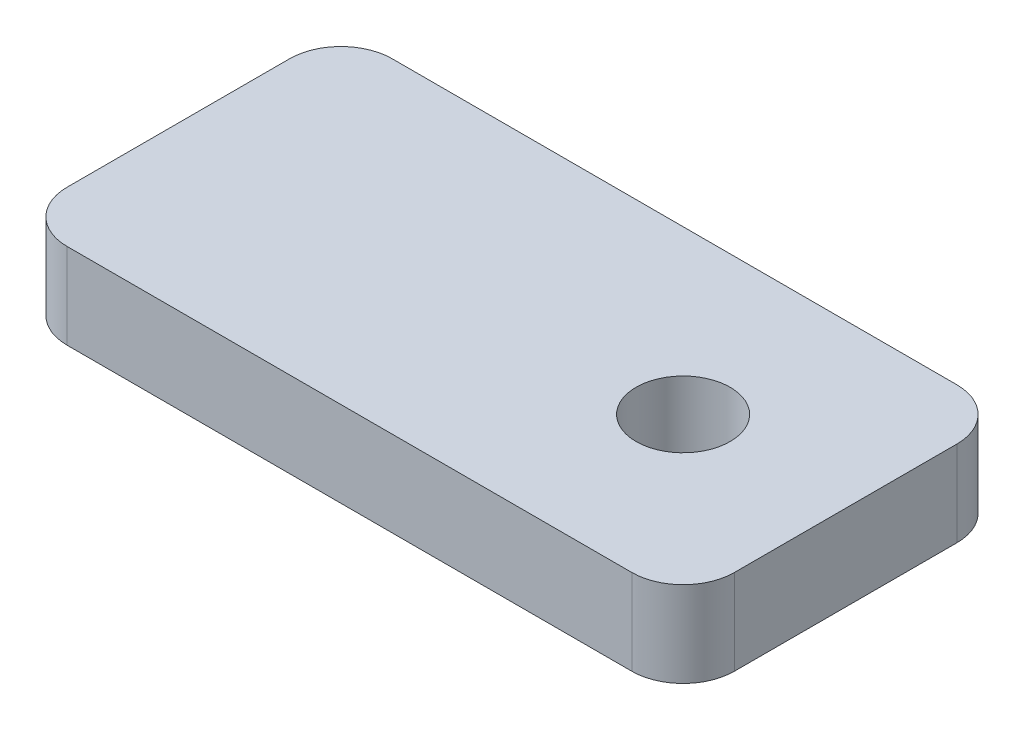
SolidWorks part; units mm, degrees
ref_plane "Top" through (0, 0, 0) normal (0, 0, 1) x (1, 0, 0)
ref_plane "Front" through (0, 0, 0) normal (0, 1, 0) x (1, 0, 0)
ref_plane "Right" through (0, 0, 0) normal (1, 0, 0) x (0, 0, -1)
sketch "Profile Sketch" plane through (0, 0, 0) normal (0, 1, 0) x (1, 0, 0)
  line L0 (0, -10) -> (0, 10) construction
  line L1 (-16.5, -9.5) -> (16.5, -9.5)
  line L2 (-19.5, -6.5) -> (-19.5, 6.5)
  line L3 (-16.5, 9.5) -> (16.5, 9.5)
  line L4 (19.5, -6.5) -> (19.5, 6.5)
  line L5 (-20, -10) -> (20, -10) construction
  line L6 (-20, -10) -> (-20, 10) construction
  line L7 (-20, 10) -> (20, 10) construction
  line L8 (20, -10) -> (20, 10) construction
  arc A0 (-16.5, -9.5) -> (-19.5, -6.5) centre (-16.5, -6.5) cw
  arc A1 (-16.5, 9.5) -> (-19.5, 6.5) centre (-16.5, 6.5) ccw
  arc A2 (19.5, 6.5) -> (16.5, 9.5) centre (16.5, 6.5) ccw
  arc A3 (16.5, -9.5) -> (19.5, -6.5) centre (16.5, -6.5) ccw
  point P24 (0, 0)
  dimension "Corner Radius" = 3
  dimension "D3" = 0.5
  dimension "D4" = 0.5
  dimension "D5" = 0.5
  dimension "D6" = 20
  dimension "D11" = 20
  dimension "D12" = 20
  dimension "D2" = 19.5
extrude "Profile" add sketch "Profile Sketch" against normal blind 5
sketch "Extension Sketch" plane through (0, 0, 0) normal (0, 1, 0) x (1, 0, 0)
  line L0 (-14.5, 9.5) -> (-16.5, 9.5)
  line L1 (-19.5, 6.5) -> (-19.5, -6.5)
  line L2 (-16.5, -9.5) -> (-14.5, -9.5)
  line L3 (-14.5, -9.5) -> (-14.5, 9.5)
  line L4 (-19.5, -6.5) -> (-19.5, 6.5) construction
  line L5 (-16.5, 9.5) -> (16.5, 9.5) construction
  line L6 (-16.5, -9.5) -> (16.5, -9.5) construction
  arc A0 (-19.5, -6.5) -> (-16.5, -9.5) centre (-16.5, -6.5) ccw
  arc A1 (-19.5, 6.5) -> (-16.5, 9.5) centre (-16.5, 6.5) cw
  dimension "D1" = 3
  dimension "D2" = 5
extrude "Extension Extrude" [suppressed] add sketch "Extension Sketch" along normal blind 5
hole_wizard "M5 Hole" positions "M5 Position Sketch" profile "M5 Profile Sketch" hole size "M5" standard "ANSI Metric" end condition through all
sketch "M5 Position Sketch" plane through (0, 0, 0) normal (0, 1, 0) x (1, 0, 0)
  line L0 (20, 10) -> (0, -10) construction
  point P0 (10, 0)
sketch "M5 Profile Sketch" plane through (10, 0, 0) normal (1, 0, 0) x (0, 0, 1)
  line L0 (0, 0) -> (0, 5)
  line L1 (0, 5) -> (2.75, 5)
  line L2 (2.75, 5) -> (2.75, 0)
  line L5 (2.75, 0) -> (0, 0)
  line L11 (0, -6.35) -> (0, 107.95) construction
  dimension "Thru Hole Dia." = 5.5
  dimension "Thru Hole Depth" = 5
equation "\"Clearance\"= 0.5mm"
equation "\"Plate Thickness\"= 5"
equation "\"D1\"= \"Plate Thickness\""
equation "\"D1@Profile\" = \"Plate Thickness\""
equation "\"D1@Extension Sketch\" = \"Corner Radius\""
equation "\"D2@Extension Sketch\" = \"Plate Thickness\""
equation "\"D2@Profile Sketch\"=20-\"Clearance\""
